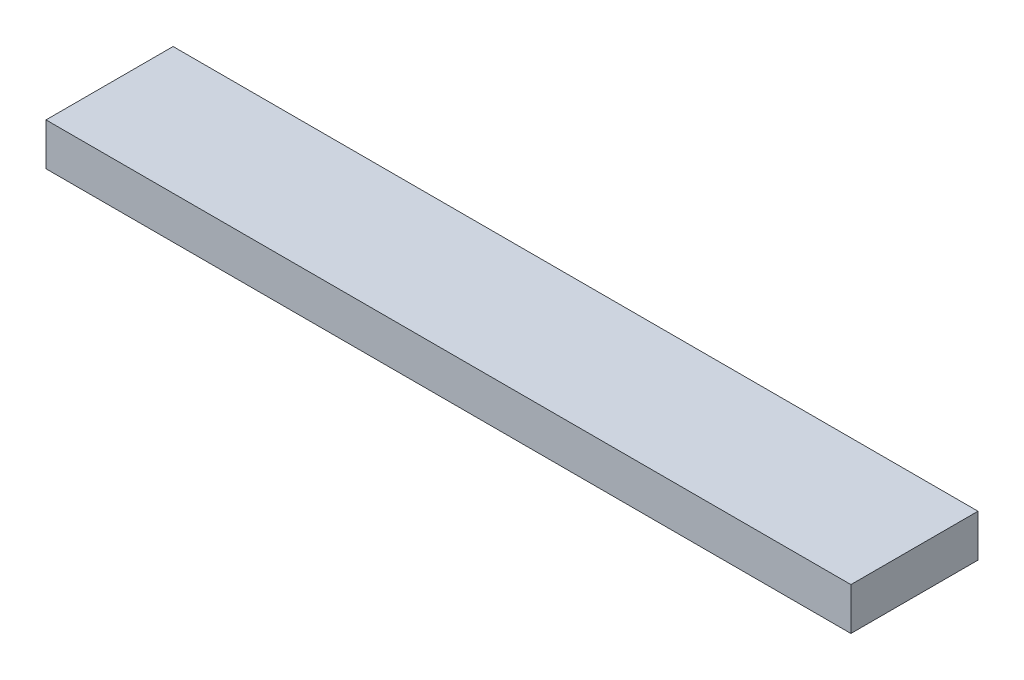
SolidWorks part; units mm, degrees
ref_plane "Ebene vorne" through (0, 0, 0) normal (0, 0, 1) x (1, 0, 0)
ref_plane "Ebene oben" through (0, 0, 0) normal (0, 1, 0) x (1, 0, 0)
ref_plane "Ebene rechts" through (0, 0, 0) normal (1, 0, 0) x (0, 0, -1)
sketch "Skizze1" plane through (0, 0, 0) normal (1, 0, 0) x (0, 0, -1)
  line L1 (0, 0) -> (150, 0)
  line L2 (0, 0) -> (0, 50)
  line L3 (0, 50) -> (150, 50)
  line L4 (150, 0) -> (150, 50)
  dimension "D1" = 50
  dimension "D2" = 150
extrude "Aufsatz-Linear austragen1" add sketch "Skizze1" along normal blind 950
